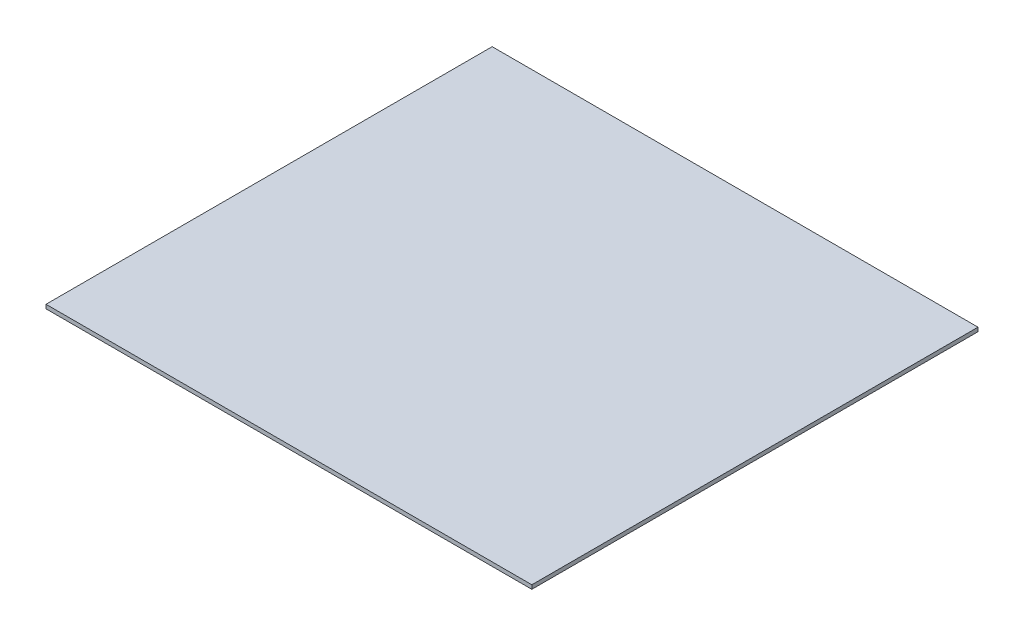
SolidWorks part; units mm, degrees
ref_plane "Płaszczyzna przednia" through (0, 0, 0) normal (0, 0, 1) x (1, 0, 0)
ref_plane "Płaszczyzna górna" through (0, 0, 0) normal (0, 1, 0) x (1, 0, 0)
ref_plane "Płaszczyzna prawa" through (0, 0, 0) normal (1, 0, 0) x (0, 0, -1)
sketch "Szkic1" plane through (0, 0, 0) normal (0, 1, 0) x (1, 0, 0)
  line L1 (-245, 225) -> (245, 225)
  line L2 (-245, 225) -> (-245, -225)
  line L3 (-245, -225) -> (245, -225)
  line L4 (245, 225) -> (245, -225)
  line L5 (-245, 225) -> (245, -225) construction
  line L6 (-245, -225) -> (245, 225) construction
  point P0 (0, 0)
  dimension "D1" = 490
  dimension "D2" = 450
base flange "Odgięcie bazowe1" sketch "Szkic1" thickness 4 reverse thickness direction no parameters "D1"=0.7366
sketch "Linie zgięcia1" [suppressed] plane through (0, 0, 0) normal (0, 1, 0) x (1, 0, 0)
sketch "Ramka-graniczna1" [suppressed] plane through (0, 0, 0) normal (0, 1, 0) x (1, 0, 0)
sheet metal parameters "Arkusz blachy2" thickness 4 parameters "D1"=0.7366
flat pattern "Rozłożony model2" [suppressed]
sketch "Linie zgięcia2" plane through (0, 0, 0) normal (0, 1, 0) x (1, 0, 0)
sketch3d "Ramka-graniczna2" [suppressed]
  line L0 (-245, 320, 0) -> (-245, -320, 0) construction
  line L1 (245, 320, 0) -> (245, -320, 0) construction
  line L2 (-245, 320, 0) -> (245, 320, 0) construction
  line L3 (-245, -320, 0) -> (245, -320, 0) construction
